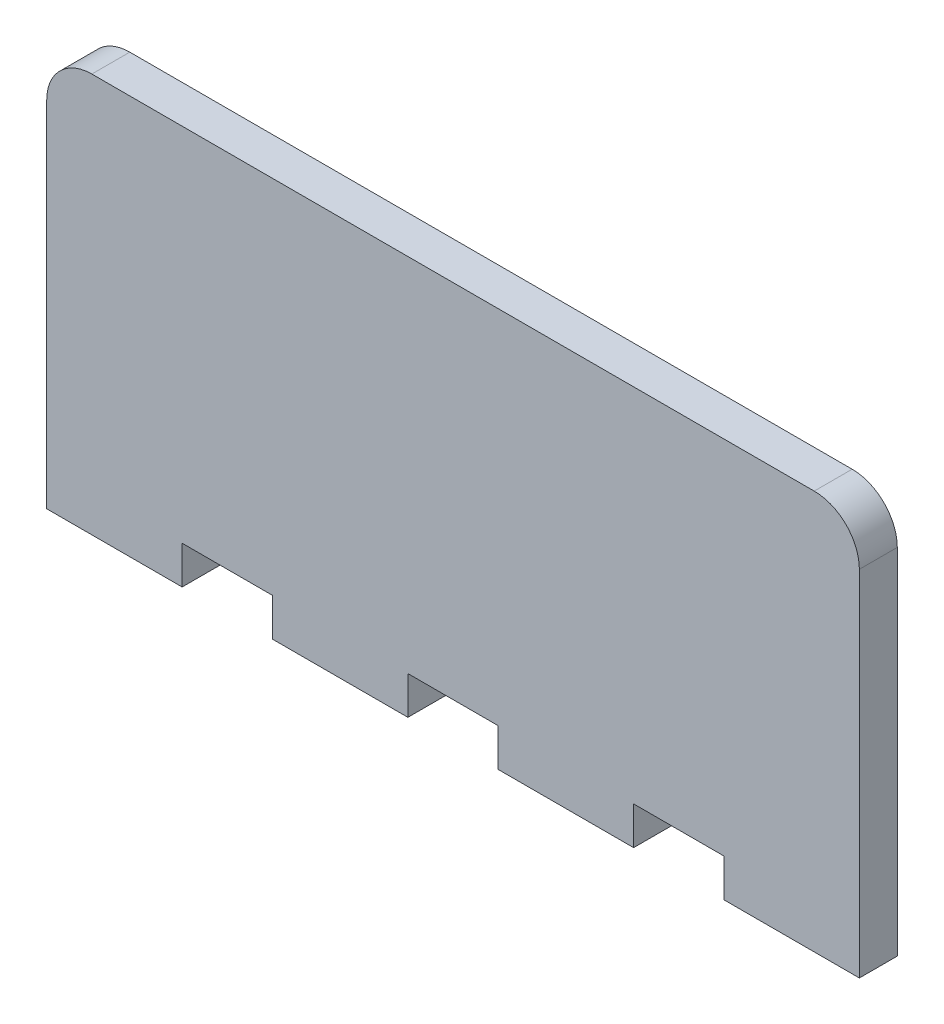
SolidWorks part; units mm, degrees
material "Teak"
ref_plane "Front Plane" through (0, 0, 0) normal (0, 0, 1) x (1, 0, 0)
ref_plane "Top Plane" through (0, 0, 0) normal (0, 1, 0) x (1, 0, 0)
ref_plane "Right Plane" through (0, 0, 0) normal (1, 0, 0) x (0, 0, -1)
sketch "Sketch1" plane through (0, 0, 0) normal (0, 0, 1) x (1, 0, 0)
  line L1 (-30.5325, 25.3111) -> (83.7675, 25.3111)
  line L2 (-30.5325, 25.3111) -> (-30.5325, -30.8229)
  line L3 (-30.5325, -30.8229) -> (83.7675, -30.8229)
  line L4 (83.7675, 25.3111) -> (83.7675, -30.8229)
  dimension "D1" = 56.134
  dimension "D2" = 114.3
extrude "Boss-Extrude1" add sketch "Sketch1" along normal blind 5.334 contours L1 L4 L3 L2
sketch "Sketch2" plane through (0, 0, 5.334) normal (0, 0, 1) x (1, 0, 0)
  line L0 (-30.5325, -30.8229) -> (83.7675, -30.8229) construction
  line L1 (-11.4825, -30.8229) -> (1.2175, -30.8229)
  line L2 (-11.4825, -30.8229) -> (-11.4825, -25.4889)
  line L3 (-11.4825, -25.4889) -> (1.2175, -25.4889)
  line L4 (1.2175, -30.8229) -> (1.2175, -25.4889)
  line L5 (-11.4825, -25.4889) -> (-30.5325, -25.4889) construction
  line L6 (20.2675, -30.8229) -> (32.9675, -30.8229)
  line L7 (20.2675, -30.8229) -> (20.2675, -25.4889)
  line L8 (20.2675, -25.4889) -> (32.9675, -25.4889)
  line L9 (32.9675, -30.8229) -> (32.9675, -25.4889)
  line L10 (52.0175, -30.8229) -> (64.7175, -30.8229)
  line L11 (52.0175, -30.8229) -> (52.0175, -25.4889)
  line L12 (52.0175, -25.4889) -> (64.7175, -25.4889)
  line L13 (64.7175, -30.8229) -> (64.7175, -25.4889)
  line L14 (-30.5325, 25.3111) -> (-30.5325, -30.8229) construction
  line L15 (1.2175, -25.4889) -> (20.2675, -25.4889) construction
  line L16 (32.9675, -25.4889) -> (52.0175, -25.4889) construction
  line L17 (64.7175, -25.4889) -> (83.7675, -25.4889) construction
  line L18 (83.7675, 25.3111) -> (83.7675, -30.8229) construction
  dimension "D1" = 19.05
  dimension "D2" = 12.7
  dimension "D3" = 19.05
  dimension "D4" = 12.7
  dimension "D5" = 19.05
  dimension "D6" = 12.7
  dimension "D7" = 19.05
  dimension "D8" = 5.334
extrude "Cut-Extrude1" cut sketch "Sketch2" against normal through all
fillet "Fillet1" radius 6.35 2 edges at (83.7675, 25.3111, 2.667) (-30.5325, 25.3111, 2.667)
equation "\"MDF\"= .21in"
equation "\"Foamcore\"= .13in"
equation "\"Gmaterial\"= \"MDF\""
equation "\"D1@Sketch1\"=\"MDF\"+2"
equation "\"D1@Boss-Extrude1\"=\"MDF\""
equation "\"D8@Sketch2\"=\"MDF\""
